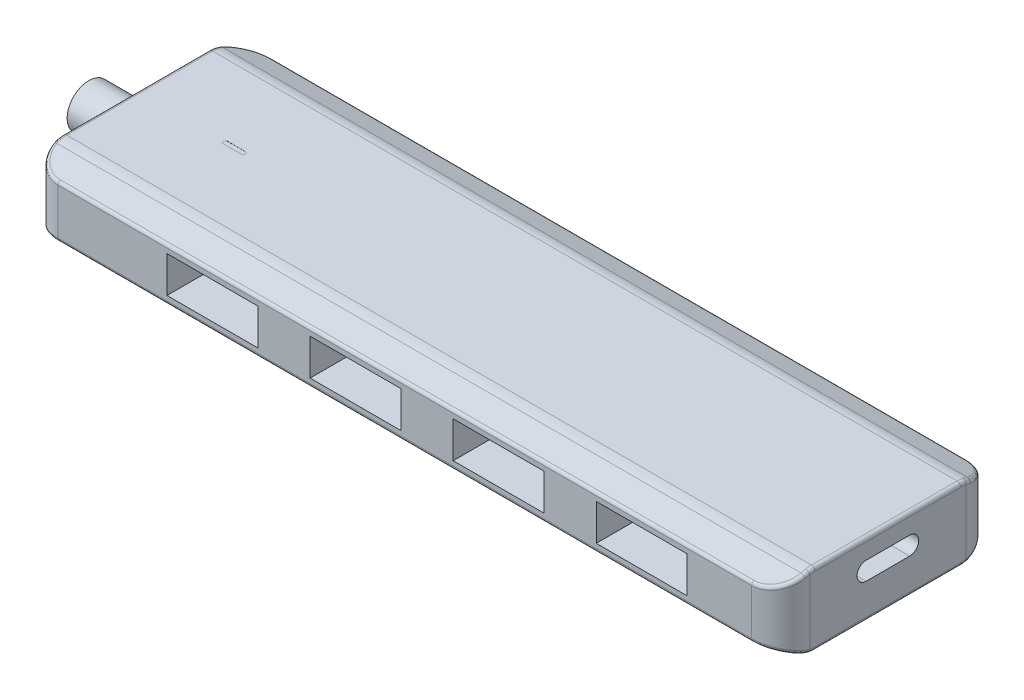
SolidWorks part; units mm, degrees
ref_plane "前视基准面" through (0, 0, 0) normal (0, 0, 1) x (1, 0, 0)
ref_plane "上视基准面" through (0, 0, 0) normal (0, 1, 0) x (1, 0, 0)
ref_plane "右视基准面" through (0, 0, 0) normal (1, 0, 0) x (0, 0, -1)
sketch "草图1" plane through (0, 0, 0) normal (0, 1, 0) x (1, 0, 0)
  line L0 (38.5543, 26.1878) -> (142.0543, 26.1878)
  line L1 (142.0543, 26.1878) -> (142.0543, 55.6878)
  line L2 (142.0543, 55.6878) -> (38.5543, 55.6878)
  line L3 (38.5543, 55.6878) -> (38.5543, 26.1878)
extrude "凸台-拉伸1" add sketch "草图1" along normal blind 10
fillet "圆角1" radius 4 4 edges at (38.5543, 5, -26.1878) (38.5543, 5, -55.6878) (142.0543, 5, -26.1878) (142.0543, 5, -55.6878)
sketch "草图2" plane through (142.0543, 0, 0) normal (1, 0, 0) x (0, 0, -1)
  line L0 (26.1878, 10) -> (26.1878, 8.5)
  line L1 (26.1878, 0) -> (26.1878, 10) construction
  line L2 (26.1878, 10) -> (30.1878, 10)
  line L3 (30.1878, 10) -> (51.6878, 10) construction
  line L4 (30.1878, 10) -> (26.1878, 8.5)
  line L6 (30.1878, 0) -> (26.1878, 1.5)
  line L7 (26.1878, 0) -> (30.1878, 0)
  line L8 (26.1878, 0) -> (26.1878, 1.5)
  line L9 (55.6878, 0) -> (55.6878, 1.5)
  line L10 (55.6878, 0) -> (51.6878, 0)
  line L11 (51.6878, 0) -> (55.6878, 1.5)
  line L12 (51.6878, 10) -> (55.6878, 8.5)
  line L13 (55.6878, 10) -> (51.6878, 10)
  line L14 (55.6878, 10) -> (55.6878, 8.5)
extrude "切除-拉伸1" cut sketch "草图2" against normal through all
fillet "圆角2" radius 4 4 edges at (90.3043, 0, -51.6878) (90.3043, 0, -30.1878) (90.3043, 10, -51.6878) (90.3043, 10, -30.1878)
sketch "草图3" plane through (38.5543, 0, 0) normal (-1, 0, 0) x (0, 0, 1)
  circle A0 centre (-40.9378, 5) radius 3
extrude "凸台-拉伸2" add sketch "草图3" along normal blind 6.5
sketch "草图4" plane through (0, 0, -26.1878) normal (0, 0, 1) x (1, 0, 0)
  line L2 (57.5543, 5) -> (57.5543, 7.5)
  line L3 (57.5543, 7.5) -> (70.0543, 7.5)
  line L4 (70.0543, 7.5) -> (70.0543, 2.5)
  line L5 (70.0543, 2.5) -> (57.5543, 2.5)
  line L6 (57.5543, 2.5) -> (57.5543, 5)
  line L8 (89.7543, 7.5) -> (89.7543, 2.5)
  line L9 (89.7543, 2.5) -> (77.2543, 2.5)
  line L10 (77.2543, 2.5) -> (77.2543, 5)
  line L11 (77.2543, 5) -> (77.2543, 7.5)
  line L12 (77.2543, 7.5) -> (89.7543, 7.5)
  line L13 (109.4543, 7.5) -> (109.4543, 2.5)
  line L14 (96.9543, 7.5) -> (109.4543, 7.5)
  line L15 (109.4543, 2.5) -> (96.9543, 2.5)
  line L16 (96.9543, 2.5) -> (96.9543, 5)
  line L17 (96.9543, 5) -> (96.9543, 7.5)
  line L20 (116.6543, 2.5) -> (116.6543, 5)
  line L21 (116.6543, 7.5) -> (129.1543, 7.5)
  line L22 (116.6543, 5) -> (116.6543, 7.5)
  line L23 (129.1543, 2.5) -> (116.6543, 2.5)
  line L24 (129.1543, 7.5) -> (129.1543, 2.5)
extrude "切除-拉伸2" cut sketch "草图4" against normal blind 6.5
sketch "草图5" plane through (142.0543, 0, 0) normal (1, 0, 0) x (0, 0, -1)
  line L3 (40.9378, 4.8) -> (37.9378, 4.8)
  line L5 (37.9378, 7.3) -> (43.9378, 7.3)
  line L7 (43.9378, 4.8) -> (40.9378, 4.8)
  arc A0 (37.9378, 7.3) -> (37.9378, 4.8) centre (37.9378, 6.05) ccw
  arc A1 (43.9378, 4.8) -> (43.9378, 7.3) centre (43.9378, 6.05) ccw
extrude "切除-拉伸3" cut sketch "草图5" against normal blind 6.5
sketch "草图6" plane through (0, 10, 0) normal (0, 1, 0) x (1, 0, 0)
  line L4 (53.2543, 41.2378) -> (50.8543, 41.2378)
  line L6 (50.8543, 40.6378) -> (53.2543, 40.6378)
  arc A0 (50.8543, 40.6378) -> (50.8543, 41.2378) centre (50.8543, 40.9378) cw
  arc A1 (53.2543, 40.6378) -> (53.2543, 41.2378) centre (53.2543, 40.9378) ccw
extrude "切除-拉伸4" cut sketch "草图6" against normal blind 0.01
fillet "圆角3" radius 0.5 32 edges at (39.9772, 1.1472, -27.1287) (38.5543, 0.0166, -30.549) (38.5543, 0, -40.9378) (38.5543, 0.0166, -51.3267) (39.9772, 1.1472, -54.747) (90.3043, 1.5, -55.6878) (140.6315, 1.1472, -54.747) (142.0543, 0.0166, -51.3267) (142.0543, 0, -40.9378) (142.0543, 0.0166, -30.549) (140.6315, 1.1472, -27.1287) (39.9772, 8.8528, -27.1287) (38.5543, 9.9834, -30.549) (38.5543, 10, -40.9378) (38.5543, 9.9834, -51.3267) (39.9772, 8.8528, -54.747) (90.3043, 8.5, -55.6878) (140.6315, 8.8528, -54.747) (142.0543, 9.9834, -51.3267) (142.0543, 10, -40.9378) (142.0543, 9.9834, -30.549) (140.6315, 8.8528, -27.1287) (90.3043, 1.5, -26.1878) (90.3043, 8.5, -26.1878)
